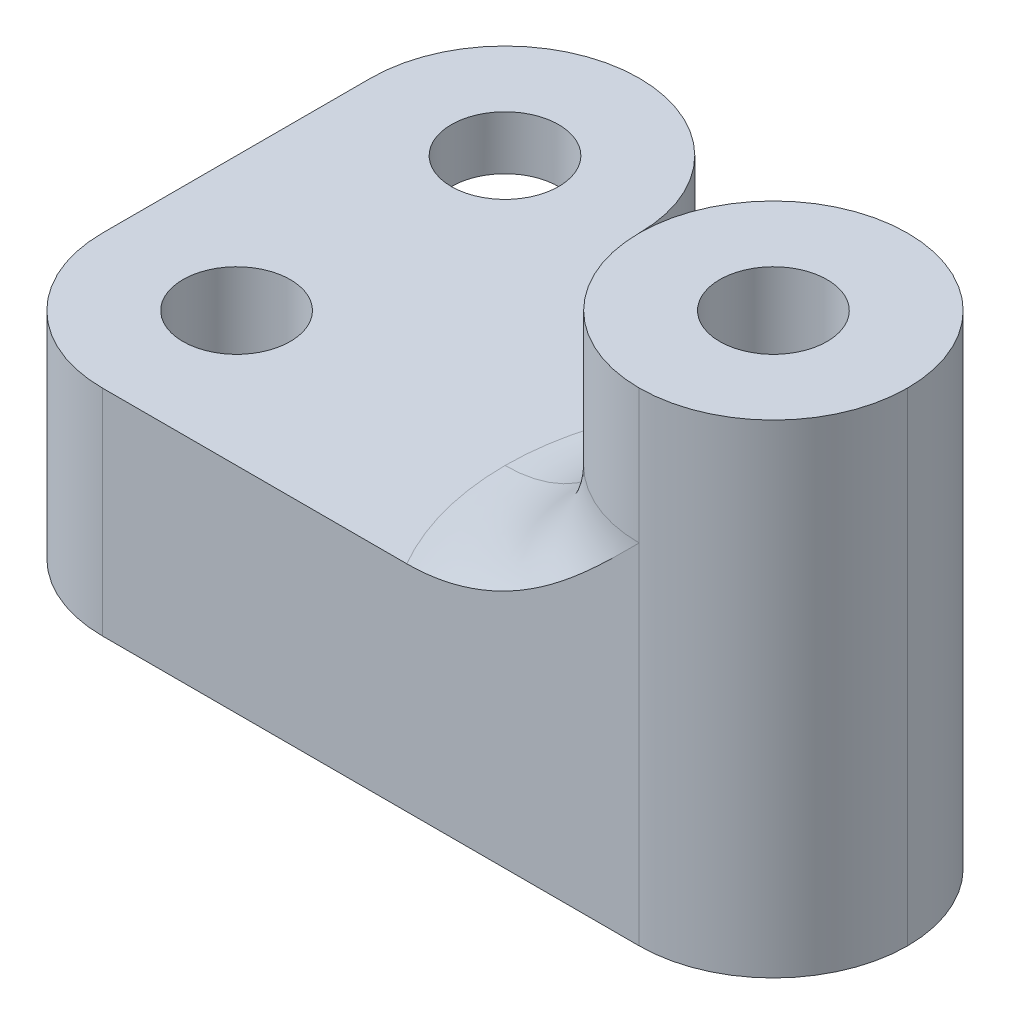
SolidWorks part; units mm, degrees
material "Balsa"
ref_plane "Alzado" through (0, 0, 0) normal (0, 0, 1) x (1, 0, 0)
ref_plane "Planta" through (0, 0, 0) normal (0, 1, 0) x (1, 0, 0)
ref_plane "Vista lateral" through (0, 0, 0) normal (1, 0, 0) x (0, 0, -1)
sketch "Croquis1" plane through (0, 0, 0) normal (0, 1, 0) x (1, 0, 0)
  line L0 (0, 0) -> (0, 10)
  line L1 (0, 10) -> (5, 10)
  line L2 (5, 10) -> (5, 5)
  line L3 (5, 5) -> (15, 5)
  line L4 (15, 5) -> (15, 0)
  line L5 (15, 0) -> (0, 0)
  dimension "D1" = 15
  dimension "D2" = 10
  dimension "D3" = 5
  dimension "D4" = 5
extrude "Saliente-Extruir1" add sketch "Croquis1" along normal blind 4
sketch "Croquis2" plane through (0, 4, 0) normal (0, 1, 0) x (1, 0, 0)
  line L0 (0, 10) -> (5, 5) construction
  line L1 (5, 5) -> (0, 0) construction
  line L2 (15, 0) -> (10, 5) construction
  line L3 (15, 5) -> (5, 5) construction
  line L4 (5, 10) -> (0, 5) construction
  line L5 (0, 10) -> (0, 0) construction
  line L6 (0, 5) -> (5, 0) construction
  line L7 (0, 0) -> (15, 0) construction
  line L8 (15, 5) -> (10, 0) construction
  line L9 (15, 0) -> (15, 5) construction
  circle A0 centre (2.5, 7.5) radius 1
  circle A1 centre (2.5, 2.5) radius 1
  circle A2 centre (12.5, 2.5) radius 1
  dimension "D2" = 2
  dimension "D3" = 2
  dimension "D4" = 2
  dimension "D1" = 45
extrude "Cortar-Extruir1" cut sketch "Croquis2" against normal blind 5
sketch "Croquis3" plane through (0, 4, 0) normal (0, 1, 0) x (1, 0, 0)
  line L1 (10, 5) -> (15, 5)
  line L2 (10, 5) -> (10, 0)
  line L3 (10, 0) -> (15, 0)
  line L4 (15, 5) -> (15, 0)
  line L5 (10, 5) -> (15, 0) construction
  line L6 (10, 0) -> (15, 5) construction
  circle A0 centre (12.5, 2.5) radius 1 construction
  circle A1 centre (12.5, 2.5) radius 1
  point P0 (12.5, 2.5)
extrude "Saliente-Extruir2" add sketch "Croquis3" along normal blind 5
sketch "Croquis4" plane through (0, 0, -10) normal (0, 0, -1) x (-1, 0, 0)
  line L0 (0, 2) -> (-5, 2) construction
  line L1 (0, 4) -> (0, 0) construction
  line L2 (-5, 4) -> (-5, 0) construction
  line L4 (0, 3) -> (-5, 3)
  line L5 (0, 3) -> (0, 1)
  line L6 (0, 1) -> (-5, 1)
  line L7 (-5, 3) -> (-5, 1)
  line L8 (0, 3) -> (-5, 1) construction
  line L9 (0, 1) -> (-5, 3) construction
  point P6 (-2.5, 2)
  dimension "D1" = 2
extrude "Cortar-Extruir2" cut sketch "Croquis4" against normal blind 5
fillet "Redondeo1" radius 2.5 11 edges at (0, 2, 0) (10, 6.5, 0) (10, 6.5, -5) (15, 4.5, 0) (15, 4.5, -5) (5, 0.5, -5) (5, 3.5, -5) (0, 0.5, -10) (5, 0.5, -10) (5, 3.5, -10) (0, 3.5, -10)
fillet "Redondeo2" radius 2.5 2 edges at (10.7322, 4, -4.2678) (10.7322, 4, -0.7322)
